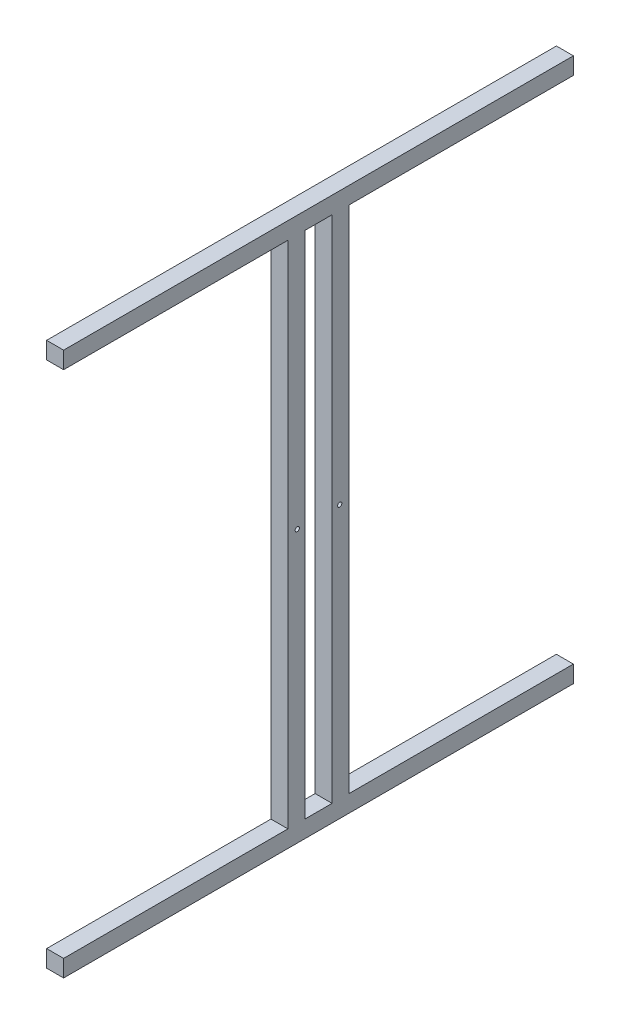
SolidWorks part; units mm, degrees
ref_plane "Front" through (0, 0, 0) normal (0, 0, 1) x (1, 0, 0)
ref_plane "Top" through (0, 0, 0) normal (0, 1, 0) x (1, 0, 0)
ref_plane "Right" through (0, 0, 0) normal (1, 0, 0) x (0, 0, -1)
sketch "Sketch1" plane through (0, 0, 0) normal (1, 0, 0) x (0, 0, -1)
  line L0 (-600, -500) -> (-600, -520)
  line L1 (0, -500) -> (-600, -500)
  line L2 (0, -500) -> (0, -520)
  line L3 (-600, -520) -> (-600, -1120) construction
  line L4 (-600, -1120) -> (-600, -1140)
  line L5 (0, -1120) -> (-600, -1120)
  line L6 (0, -1120) -> (0, -1140)
  line L7 (0, -520) -> (-600, -520)
  line L8 (0, -1140) -> (-600, -1140)
  line L9 (-300, -520) -> (-300, -1120) construction
  line L10 (-300, -1120) -> (-359.4936, -1171.8985) construction
  line L11 (-316, -520) -> (-316, -1120)
  line L12 (20, 0) -> (0, 0)
  line L13 (-600, 0) -> (-620, 0)
  line L14 (20, -1300) -> (0, -1300)
  line L15 (-600, -1300) -> (-620, -1300)
  line L16 (-284, -520) -> (-284, -1120)
  line L17 (-336, -520) -> (-336, -1120)
  line L18 (-264, -520) -> (-264, -1120)
  line L19 (-600, -820) -> (75.2731, -820) construction
  circle A0 centre (-300, -820) radius 36 construction
  dimension "D1" = 600
  dimension "D2" = 600
  dimension "D3" = 2
  dimension "D4" = 16
  dimension "D5" = 20
  dimension "D6" = 16
  dimension "D7" = 20
  dimension "D8" = 20
extrude "Boss-Extrude1" add sketch "Sketch1" along normal blind 20 contours L14 L12 L1 L13 L15 L7 | L7 L17 L5 L11 | L18 L7 L16 L5 | L5 L4 L8 L6 region at (0, -510, 300) region at (0, -820, 326) region at (0, -820, 274)
sketch "Sketch3" plane through (20, 0, 0) normal (1, 0, 0) x (0, 0, -1)
  circle A0 centre (-325, -820) radius 2.5
  circle A1 centre (-275, -820) radius 2.5
extrude "Cut-Extrude1" cut sketch "Sketch3" against normal through all both and the other way through all
